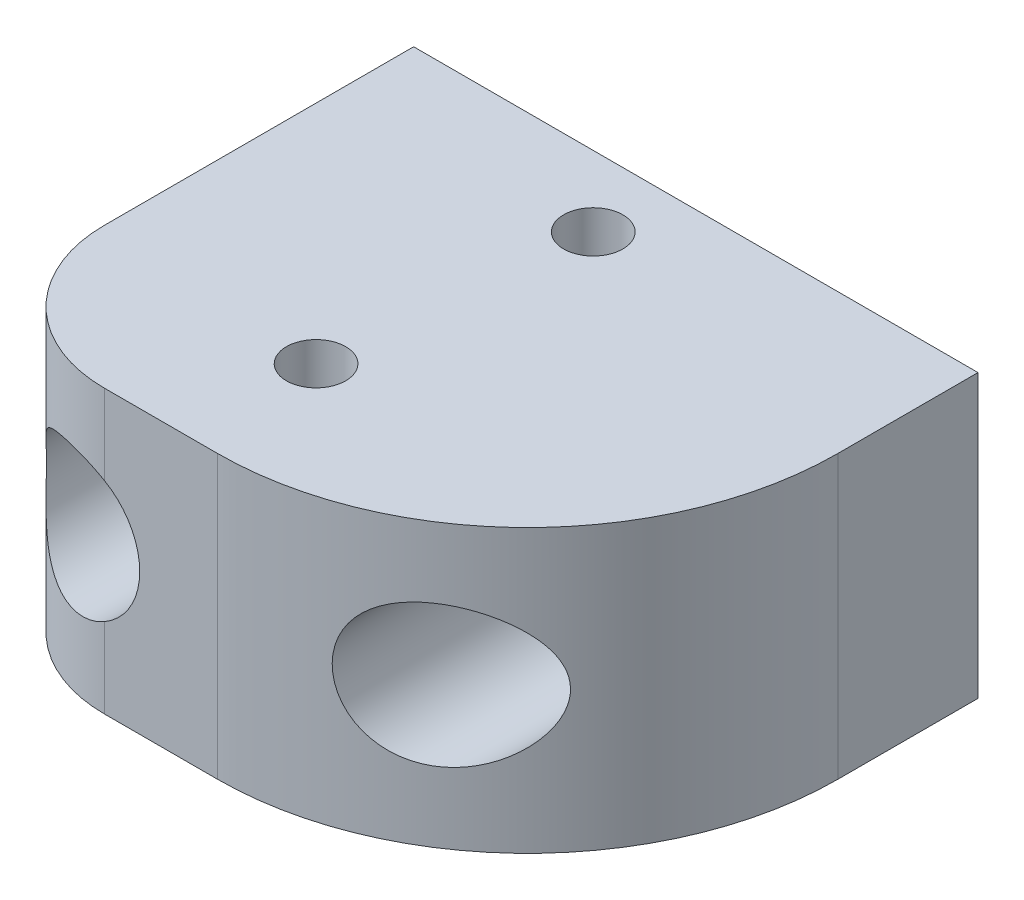
SolidWorks part; units mm, degrees
ref_plane "Front Plane" through (0, 0, 0) normal (0, 0, 1) x (1, 0, 0)
ref_plane "Top Plane" through (0, 0, 0) normal (0, 1, 0) x (1, 0, 0)
ref_plane "Right Plane" through (0, 0, 0) normal (1, 0, 0) x (0, 0, -1)
sketch "Sketch1" plane through (0, 0, 0) normal (0, 1, 0) x (1, 0, 0)
  line L0 (-9.23, -17.9167) -> (-9.23, 2.8517) construction
  line L1 (-6, 0) -> (-6, 9.4264) construction
  circle A0 centre (0, 0) radius 6
  circle A1 centre (-1.73, -17.9167) radius 7.5
  circle A2 centre (-1.73, -17.9167) radius 9
  circle A3 centre (0, 0) radius 9
  dimension "D1" = 12
  dimension "D2" = 15
  dimension "D3" = 18
  dimension "D4" = 3.23
sketch "Sketch2" plane through (0, 0, 0) normal (0, 1, 0) x (1, 0, 0)
  line L0 (-9.23, -17.9167) -> (-9.23, 2.8517) construction
  line L1 (-17.73, 5) -> (22.27, 5)
  line L2 (-17.73, 5) -> (-17.73, -26.9167)
  line L3 (-17.73, -26.9167) -> (22.27, -26.9167)
  line L4 (22.27, 5) -> (22.27, -26.9167)
  circle A0 centre (-1.73, -17.9167) radius 9 construction
  dimension "D1" = 5
  dimension "D2" = 8.5
  dimension "D3" = 40
extrude "Boss-Extrude1" add sketch "Sketch2" against normal blind 20
sketch "Sketch3" plane through (0, 0, 26.9167) normal (0, 0, 1) x (1, 0, 0)
  line L0 (-17.73, -10) -> (22.27, -10) construction
  line L1 (-17.73, -20) -> (-17.73, 0) construction
  line L2 (22.27, -20) -> (22.27, 0) construction
  point P6 (12.27, -10)
  point P7 (-10.23, -10)
  dimension "D1" = 10
  dimension "D2" = 7.5
hole_wizard "CBORE for M5 SHCS1" positions "Sketch4" profile "Sketch5" counterbore size "M5" standard "ANSI Metric" end condition up to next
sketch "Sketch4" plane through (0, 0, 26.9167) normal (0, 0, 1) x (1, 0, 0)
  point P0 (-10.23, -10)
  point P3 (12.27, -10)
sketch "Sketch5" plane through (-10.23, -10, 26.9167) normal (1, 0, 0) x (0, -1, 0)
  line L0 (0, 0) -> (0, 31.9167)
  line L1 (0, 31.9167) -> (2.75, 31.9167)
  line L3 (2.75, 31.9167) -> (2.75, 25)
  line L4 (2.75, 25) -> (5, 25)
  line L5 (5, 25) -> (5, 0)
  line L7 (5, 0) -> (0, 0)
  line L11 (0, -6.35) -> (0, 107.95) construction
  dimension "Thru Hole Dia." = 5.5
  dimension "Thru Hole Depth" = 31.9167
  dimension "C'Bore Dia." = 10
  dimension "C'Bore Depth" = 25
hole_wizard "M5x0.8 Tapped Hole1" positions "Sketch7" profile "Sketch8" tap size "M5x0.8" standard "ANSI Metric" end condition up to next
sketch "Sketch7" plane through (0, 0, 0) normal (0, 1, 0) x (1, 0, 0)
  point P0 (-1.73, -17.9167)
  point P3 (0, 0)
sketch "Sketch8" plane through (-1.73, 0, 17.9167) normal (1, 0, 0) x (0, 0, 1)
  line L0 (0, 0) -> (0, 20)
  line L1 (0, 20) -> (2.1, 20)
  line L2 (2.1, 20) -> (2.1, 0)
  line L5 (2.1, 0) -> (0, 0)
  line L11 (0, -6.35) -> (0, 107.95) construction
  dimension "Thru Tap Drill Dia." = 4.2
  dimension "Thru Tap Drill Depth" = 20
cosmetic thread "Hole Thread1" parameters "D2"=5
cosmetic thread "Hole Thread2" parameters "D2"=5
fillet "Fillet1" radius 22 1 edges at (22.27, -10, 26.9167)
fillet "Fillet2" radius 10 1 edges at (-17.73, -10, 26.9167)
